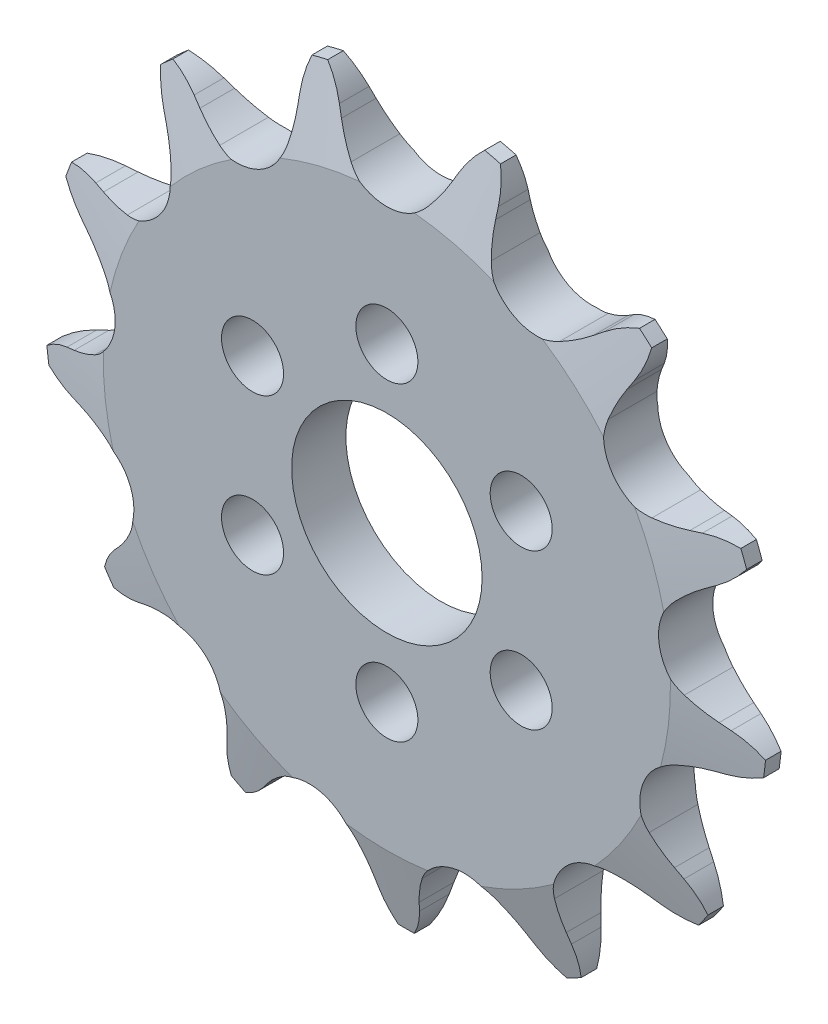
SolidWorks part; units mm, degrees
material "AISI 4130 Steel, annealed at 865C"
ref_plane "Front Plane" through (0, 0, 0) normal (0, 0, 1) x (1, 0, 0)
ref_plane "Top Plane" through (0, 0, 0) normal (0, 1, 0) x (1, 0, 0)
ref_plane "Right Plane" through (0, 0, 0) normal (1, 0, 0) x (0, 0, -1)
sketch "Sketch0" plane through (0, 0, 0) normal (0, 0, 1) x (1, 0, 0)
  line L0 (7.9375, -32.2037) -> (0, 0) construction
  line L1 (0, 0) -> (21.9941, -24.8262) construction
  line L2 (0, 0) -> (-7.9375, -32.2037) construction
  line L3 (7.9375, -32.2037) -> (21.9941, -24.8262) construction
  line L4 (7.9375, -32.2037) -> (-7.9375, -32.2037) construction
  line L5 (13.9545, -31.0679) -> (13.2815, -30.2592)
  line L6 (7.9375, -32.2037) -> (0, -34.1601) construction
  line L7 (2.0819, -33.9942) -> (2.302, -32.9654)
  line L8 (0, -32.2037) -> (0, -36.9662) construction
  line L9 (10.986, -28.0897) -> (3.0984, -38.7342) construction
  line L10 (0, 0) -> (0, -32.2037) construction
  line L11 (13.2815, -30.2592) -> (3.0984, -38.7342) construction
  line L12 (0, -36.9662) -> (0, -38.0102) construction
  line L13 (20.5322, -25.5935) -> (13.9545, -31.0679) construction
  circle A0 centre (0, 0) radius 36.9662 construction
  circle A1 centre (0, 0) radius 33.1675 construction
  arc A2 (-7.9261, -40.603) -> (25.8874, -32.2687) centre (0, 0) ccw
  circle A3 centre (0, 0) radius 38.0102 construction
  circle A4 centre (7.9375, -32.2037) radius 5.08 construction
  arc A7 (10.986, -28.0897) -> (3.3263, -29.9776) centre (7.9375, -32.2037) ccw
  circle A8 centre (7.9375, -32.2037) radius 5.1204 construction
  arc A9 (13.9545, -31.0679) -> (25.8874, -32.2687) centre (20.5322, -25.5935) ccw
  arc A10 (13.2815, -30.2592) -> (10.986, -28.0897) centre (3.0984, -38.7342) ccw
  arc A11 (2.0819, -33.9942) -> (-7.9261, -40.603) centre (-6.2865, -32.2037) cw
  arc A12 (2.302, -32.9654) -> (3.3263, -29.9776) centre (15.2572, -35.7373) cw
  dimension "D1" = 5.1204
  dimension "R" = 5.1204
sketch "Sketch1" plane through (0, 0, 0) normal (1, 0, 0) x (0, 0, -1)
  line L0 (2.7781, 0) -> (-2.7781, 0)
  line L1 (-2.7781, 0) -> (-2.7781, 29.0287)
  line L2 (-2.7781, 29.0287) -> (-0.7937, 36.9662)
  line L3 (-0.7937, 36.9662) -> (0.7937, 36.9662)
  line L4 (0.7937, 36.9662) -> (2.7781, 29.0287)
  line L5 (2.7781, 29.0287) -> (2.7781, 0)
  line L7 (0, 36.9662) -> (0, 0) construction
  line L8 (-2.7781, 29.0287) -> (2.7781, 29.0287) construction
  line L9 (0, 36.9662) -> (0, -36.9662) construction
  line L10 (-2.7781, 29.0287) -> (-2.7781, 36.9662) construction
  line L11 (-2.7781, 36.9662) -> (-0.7937, 36.9662) construction
  line L12 (0.7937, 36.9662) -> (2.7781, 36.9662) construction
  line L13 (2.7781, 36.9662) -> (2.7781, 29.0287) construction
revolve "Revolve1" add sketch "Sketch1" angle 360 mid plane about L0
extrude "Cut-Extrude1" cut sketch "Sketch0" against normal through all and the other way through all
pattern_circular "CirPattern1" count 13 over 360 about axis through (0, 0, -2.7781) along (0, 0, -1) of "Cut-Extrude1"
sketch "Sketch2" plane through (0, 0, 0) normal (0, 0, 1) x (1, 0, 0)
  circle A0 centre (0, 0) radius 7.9375 construction
  circle A1 centre (0, 0) radius 30.1625
  circle A2 centre (0, 0) radius 36.957 construction
  dimension "Bore" = 15.875
  dimension "Hub Dia." = 60.325
  dimension "OD" = 73.914
sketch "Sketch3" plane through (0, 0, 0) normal (0, 0, 1) x (1, 0, 0)
  circle A1 centre (0, 0) radius 9.75
  circle A2 centre (0, 0) radius 36.957 construction
  circle A3 centre (0, 0) radius 36.957
extrude "Cut-Extrude2" cut sketch "Sketch3" along normal through all and the other way through all flip side to cut
sketch "Sketch4" plane through (0, 0, -2.7781) normal (0, 0, -1) x (-1, 0, 0)
  line L0 (0, 0) -> (0, 15.875) construction
  circle A0 centre (0, 15.875) radius 3.175
  circle A1 centre (13.7482, 7.9375) radius 3.175
  circle A2 centre (13.7482, -7.9375) radius 3.175
  circle A3 centre (0, -15.875) radius 3.175
  circle A4 centre (-13.7482, -7.9375) radius 3.175
  circle A5 centre (-13.7482, 7.9375) radius 3.175
  point P17 (0, 0)
  dimension "D1" = 6
extrude "Cut-Extrude3" cut sketch "Sketch4" against normal through all
sketch "Sketch5" plane through (0, 0, 2.7781) normal (0, 0, 1) x (1, 0, 0)
  line L0 (0, 0) -> (9.75, 0) construction
  line L1 (9.75, 0) -> (11, 0) construction
  circle A0 centre (0, 0) radius 11 construction
  circle A1 centre (0, 0) radius 9.75 construction
sketch "Sketch6" plane through (0, 0, -2.7781) normal (0, 0, -1) x (-1, 0, 0)
  circle A0 centre (0, 0) radius 28.024 construction
  circle A1 centre (0, 0) radius 24.2521 construction
ref_plane "Plane1" through (-29.6883, 20.4924, 0) normal (-0.823, 0.5681, 0) x (0, 0, 1)
ref_plane "Plane2" through (-35.811, 4.3482, 0) normal (-0.9927, 0.1205, 0) x (0, 0, 1)
ref_plane "Plane3" through (-33.7298, -12.792, 0) normal (-0.935, -0.3546, 0) x (0, 0, 1)
ref_plane "Plane4" through (-23.9215, -27.0018, 0) normal (-0.6631, -0.7485, 0) x (-0.7485, 0.6631, 0)
ref_plane "Plane5" through (-8.6331, -35.0258, 0) normal (-0.2393, -0.9709, 0) x (-0.9709, 0.2393, 0)
sketch "Sketch7" plane through (-29.6883, 20.4924, 0) normal (-0.823, 0.5681, 0) x (0, 0, 1)
  line L0 (-6.5106, 0) -> (7.7601, 0)
sketch "Sketch8" plane through (-35.811, 4.3482, 0) normal (-0.9927, 0.1205, 0) x (0, 0, 1)
  line L0 (-7.786, 0) -> (10.2102, 0)
sketch "Sketch9" plane through (-33.7298, -12.792, 0) normal (-0.935, -0.3546, 0) x (0, 0, 1)
  line L0 (-7.6671, 0) -> (14.0341, 0)
  line L1 (-2.7781, 0) -> (2.7781, 0) construction
sketch "Sketch10" plane through (-23.9215, -27.0018, 0) normal (-0.6631, -0.7485, 0) x (-0.7485, 0.6631, 0)
  line L0 (0, -3.5829) -> (0, 5.4944)
sketch "Sketch11" plane through (-8.6331, -35.0258, 0) normal (-0.2393, -0.9709, 0) x (-0.9709, 0.2393, 0)
  line L0 (0, -5.4358) -> (0, 8.5188)
split line "Split Line7"
split line "Split Line8"
split line "Split Line9"
split line "Split Line10"
split line "Split Line11"
equation "\"360/N@Sketch0\" = 360/\"Teeth@CirPattern1\""
equation "\"Ds@Sketch0\" = 1.005 * \"Dr@Sketch0\" + 0.003"
equation "\"R@Sketch0\" = 1/2 * \"Ds@Sketch0\""
equation "\"A@Sketch0\" = 35 +  ( 60 / \"Teeth@CirPattern1\" ) "
equation "\"B@Sketch0\" = 18 -  ( 56 / \"Teeth@CirPattern1\" )"
equation "\"ac@Sketch0\" = 0.8 * \"Dr@Sketch0\""
equation "\"ab@Sketch0\" = 1.4 * \"Dr@Sketch0\""
equation "\"J@Sketch0\" = 0.3 * \"Pitch@Sketch0\""
equation "\"h@Sketch1\" = \"Pitch@Sketch0\" / 2"
equation "\"g@Sketch1\" = \"h@Sketch1\" / 4"
